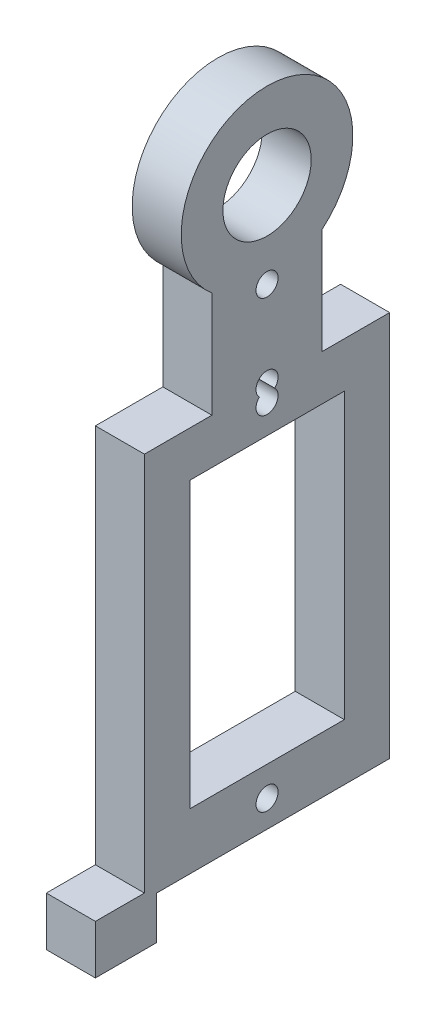
SolidWorks part; units mm, degrees
ref_plane "Front Plane" through (0, 0, 0) normal (0, 0, 1) x (1, 0, 0)
ref_plane "Top Plane" through (0, 0, 0) normal (0, 1, 0) x (1, 0, 0)
ref_plane "Right Plane" through (0, 0, 0) normal (1, 0, 0) x (0, 0, -1)
sketch "Sketch1" plane through (0, 0, 0) normal (1, 0, 0) x (0, 0, -1)
  circle A0 centre (0, 0) radius 7
extrude "Boss-Extrude1" add sketch "Sketch1" along normal blind 4
sketch "Sketch2" plane through (0, 0, 0) normal (0, 0, 1) x (1, 0, 0)
  line L1 (0, -34) -> (4, -34)
  line L2 (0, -34) -> (0, 0)
  line L3 (0, 0) -> (4, 0)
  line L4 (4, -34) -> (4, 0)
extrude "Boss-Extrude2" add sketch "Sketch2" along normal blind 9 from offset 4.5 offset against normal yes
sketch "Sketch3" plane through (0, 0, 0) normal (0, 0, 1) x (1, 0, 0)
  line L1 (0, -45.5) -> (4, -45.5)
  line L2 (0, -45.5) -> (0, -14)
  line L3 (0, -14) -> (4, -14)
  line L4 (4, -45.5) -> (4, -14)
extrude "Boss-Extrude3" add sketch "Sketch3" along normal blind 20 from offset 10 offset against normal yes
sketch "Sketch4" plane through (0, 0, 0) normal (0, 0, 1) x (1, 0, 0)
  line L1 (0, -49) -> (4, -49)
  line L2 (0, -49) -> (0, -45)
  line L3 (0, -45) -> (4, -45)
  line L4 (4, -49) -> (4, -45)
extrude "Boss-Extrude4" add sketch "Sketch4" along normal blind 5 from offset 9
sketch "Sketch5" plane through (0, 0, 0) normal (1, 0, 0) x (0, 0, -1)
  circle A0 centre (0, 0) radius 3.6
extrude "Boss-Extrude5" add sketch "Sketch5" along normal blind 6 from offset 1 separate body offset against normal yes
combine bodies "Combine1" operation type subtract main body 104 bodies to subtract 105
sketch "Sketch6" plane through (0, 0, 0) normal (1, 0, 0) x (0, 0, -1)
  circle A0 centre (0, -7) radius 0.9
extrude "Boss-Extrude6" add sketch "Sketch6" along normal blind 6 from offset 1 separate body offset against normal yes
combine bodies "Combine2" operation type subtract main body 106 bodies to subtract 107
sketch "Sketch7" plane through (0, 0, 0) normal (1, 0, 0) x (0, 0, -1)
  circle A0 centre (0, -14) radius 0.9
extrude "Boss-Extrude7" add sketch "Sketch7" along normal blind 6 from offset 1 separate body offset against normal yes
combine bodies "Combine3" operation type subtract main body 108 bodies to subtract 109
sketch "Sketch8" plane through (0, 0, 0) normal (0, 0, 1) x (1, 0, 0)
  line L1 (-1, -40.9) -> (5, -40.9)
  line L2 (-1, -40.9) -> (-1, -17.7)
  line L3 (-1, -17.7) -> (5, -17.7)
  line L4 (5, -40.9) -> (5, -17.7)
extrude "Boss-Extrude8" add sketch "Sketch8" along normal blind 12.6 from offset 6.3 separate body offset against normal yes
combine bodies "Combine4" operation type subtract main body 110 bodies to subtract 111
sketch "Sketch9" plane through (0, 0, 0) normal (1, 0, 0) x (0, 0, -1)
  circle A0 centre (0, -43.3) radius 0.9
extrude "Boss-Extrude9" add sketch "Sketch9" along normal blind 6 from offset 1 separate body offset against normal yes
combine bodies "Combine5" operation type subtract main body 112 bodies to subtract 113
sketch "Sketch10" plane through (0, 0, 0) normal (1, 0, 0) x (0, 0, -1)
  circle A0 centre (0, -15.3) radius 0.9
extrude "Boss-Extrude10" add sketch "Sketch10" along normal blind 6 from offset 1 separate body offset against normal yes
combine bodies "Combine6" operation type subtract main body 114 bodies to subtract 115
